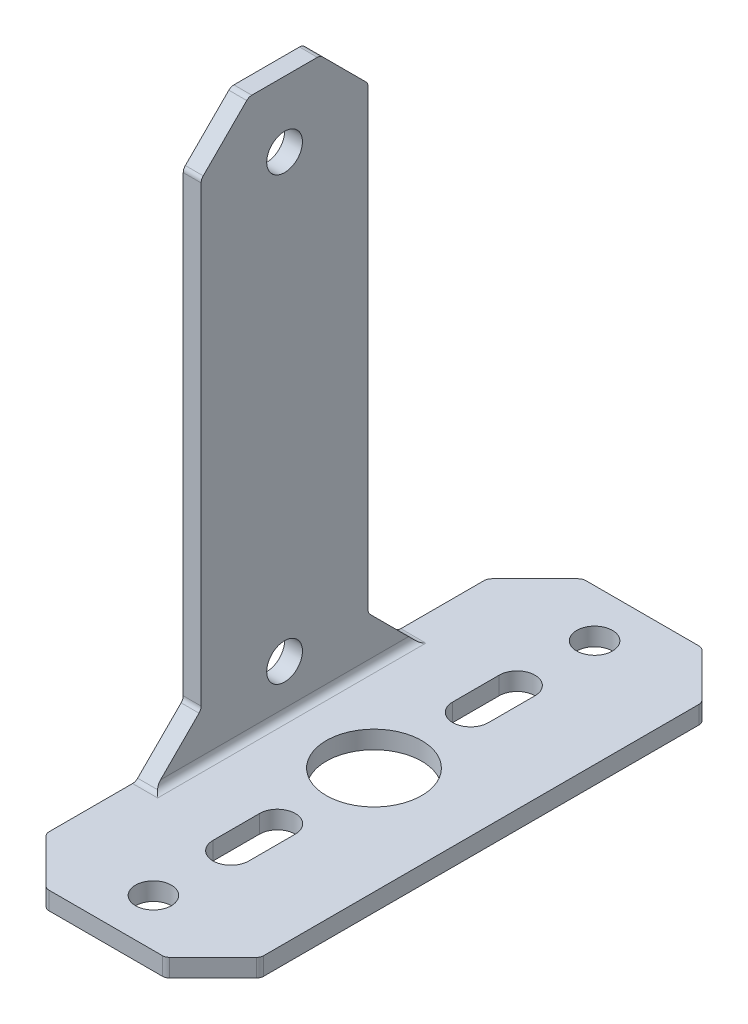
SolidWorks part; units mm, degrees
material "3.3535 (EN-AW 5754)"
ref_plane "Front" through (0, 0, 0) normal (0, 0, 1) x (1, 0, 0)
ref_plane "Top" through (0, 0, 0) normal (0, 1, 0) x (1, 0, 0)
ref_plane "Right" through (0, 0, 0) normal (1, 0, 0) x (0, 0, -1)
sketch "Эскиз1" plane through (0, 0, 0) normal (0, 0, 1) x (1, 0, 0)
  line L0 (0, 0) -> (0, 48)
  line L1 (0, 48) -> (1.5, 48)
  line L2 (1.5, 48) -> (1.5, 1.5)
  line L3 (0, 0) -> (18, 0)
  line L4 (18, 0) -> (18, 1.5)
  line L5 (18, 1.5) -> (1.5, 1.5)
  dimension "D1" = 48
  dimension "D2" = 18
  dimension "D3" = 1.5
  dimension "D4" = 1.5
extrude "Бобышка-Вытянуть1" add sketch "Эскиз1" along normal mid plane 45
sketch "Эскиз2" plane through (0, 1.5, 0) normal (0, 1, 0) x (1, 0, 0)
  line L0 (18, 0) -> (9, 0) construction
  line L1 (18, -22.5) -> (18, 22.5) construction
  line L2 (9, 0) -> (9, 6.3835) construction
  line L3 (9, 0) -> (-3.2605, 0) construction
  line L4 (7.5, 8.1) -> (7.5, 12)
  line L5 (10.5, -12) -> (10.5, -8.1)
  line L6 (10.5, 12) -> (10.5, 8.1)
  line L7 (7.5, -8.1) -> (7.5, -12)
  circle A0 centre (9, 0) radius 4
  circle A1 centre (9, 18.5) radius 1.5
  arc A2 (7.5, 8.1) -> (10.5, 8.1) centre (9, 8.1) ccw
  arc A3 (10.5, 12) -> (7.5, 12) centre (9, 12) ccw
  arc A4 (10.5, -12) -> (7.5, -12) centre (9, -12) cw
  arc A5 (7.5, -8.1) -> (10.5, -8.1) centre (9, -8.1) cw
  circle A6 centre (9, -18.5) radius 1.5
  dimension "D1" = 9
  dimension "D2" = 8
  dimension "D3" = 18.5
  dimension "D4" = 3
  dimension "D5" = 16.2
  dimension "D6" = 24
  dimension "D7" = 37
extrude "Вырез-Вытянуть1" cut sketch "Эскиз2" against normal blind 45.2
chamfer "Фаска1" distance 4 angle 45 4 edges at (18, 0.75, -22.5) (18, 0.75, 22.5) (0.75, 48, 22.5) (0.75, 48, -22.5)
sketch "Эскиз4" plane through (0, 0, 0) normal (-1, 0, 0) x (0, 0, 1)
  line L1 (0, 48) -> (0, 0) construction
  line L3 (18.5, 48) -> (-18.5, 48) construction
  circle A4 centre (0, 24) radius 18.5 construction
  circle A5 centre (0, 42.5) radius 1.5
  circle A6 centre (0, 5.5) radius 1.5
  point P11 (0, 24)
  dimension "D2" = 37
  dimension "D1" = 24
extrude "Вырез-Вытянуть2" cut sketch "Эскиз4" against normal through all contours A6 | A5 region at (0, 42.5, 0) region at (0, 5.5, 0)
sketch "Эскиз6" plane through (0, 0, 0) normal (-1, 0, 0) x (0, 0, 1)
  line L0 (0, 42.5) -> (7, 42.5)
  line L1 (7, 42.5) -> (33.3884, 42.5)
  line L2 (7, 42.5) -> (7, 72.5)
  line L3 (33.3884, 42.5) -> (33.3884, 72.5)
  line L4 (7, 72.5) -> (33.3884, 72.5)
  line L5 (7, 42.5) -> (7, 1.5)
  line L6 (7, 42.5) -> (33.1795, 42.5)
  line L7 (7, 1.5) -> (33.1795, 1.5)
  line L8 (33.1795, 42.5) -> (33.1795, 1.5)
  line L9 (0, 42.5) -> (0, 54.6433) construction
  line L10 (-33.1795, 42.5) -> (-33.1795, 1.5)
  line L11 (-7, 1.5) -> (-33.1795, 1.5)
  line L12 (-7, 42.5) -> (-33.1795, 42.5)
  line L13 (-7, 42.5) -> (-7, 1.5)
  line L14 (-7, 72.5) -> (-33.3884, 72.5)
  line L15 (-33.3884, 42.5) -> (-33.3884, 72.5)
  line L16 (-7, 42.5) -> (-7, 72.5)
  line L17 (-7, 42.5) -> (-33.3884, 42.5)
  line M7 (-22.5, 44) -> (-22.5, 0)
  line M9 (22.5, 0) -> (22.5, 44)
  line M11 (18.5, 48) -> (-18.5, 48)
  line M12 (-18.5, 48) -> (-22.5, 44)
  dimension "D1" = 41
  dimension "D2" = 30
extrude "Вырез-Вытянуть3" cut sketch "Эскиз6" against normal blind 10 contours L13 L12 L11 M7 | L12 L16 M11 M12 M7 | L17 L12 L16 L14 L15 M7 M12 M11 | L8 L1 L7 M9 | L5 L7 L1 M9 | L1 L3 L4 L2 region at (0, 22, 27.8398) region at (0, 45.1033, -14.0855) region at (0, 58.8405, -20.8548) region at (0, 22, 14.75) region at (0, 22, -14.75)
chamfer "Фаска2" distance 4 angle 45 2 edges at (0.75, 48, 7) (0.75, 48, -7)
chamfer "Фаска4" distance 4 angle 45 2 edges at (0.75, 1.5, 7) (0.75, 1.5, -7)
fillet "Скругление2" radius 0.6 13 edges at (14, 0.75, 22.5) (18, 0.75, 18.5) (18, 0.75, -18.5) (14, 0.75, -22.5) (0.75, 5.5, -7) (0.75, 44, -7) (0.75, 48, -3) (0.75, 48, 3) (0.75, 44, 7) (0.75, 5.5, 7) (0.75, 1.5, 11) (0.75, 1.5, -11) (1.5, 1.5, 0)
chamfer "Фаска5" distance 4 angle 45 2 edges at (0, 0.75, 22.5) (0, 0.75, -22.5)
fillet "Скругление3" radius 0.6 4 edges at (4, 0.75, 22.5) (0, 0.75, 18.5) (4, 0.75, -22.5) (0, 0.75, -18.5)
